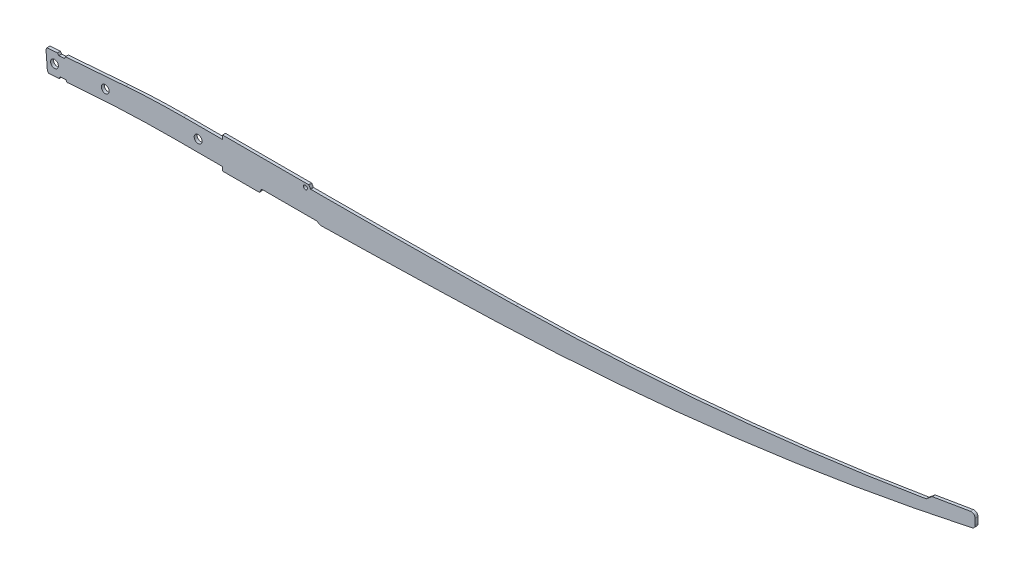
SolidWorks part; units mm, degrees
ref_plane "前视基准面" through (0, 0, 0) normal (0, 0, 1) x (1, 0, 0)
ref_plane "上视基准面" through (0, 0, 0) normal (0, 1, 0) x (1, 0, 0)
ref_plane "右视基准面" through (0, 0, 0) normal (1, 0, 0) x (0, 0, -1)
sketch "草图1" plane through (0, 0, 0) normal (0, 0, 1) x (1, 0, 0)
  line L0 (0, 81.9069) -> (0, 12) construction
  line L1 (0, 16) -> (88.2679, 16)
  line L2 (88.2679, 16) -> (90, 13)
  line L3 (0, -16) -> (37.6906, -16)
  line L4 (37.6906, -16) -> (40, -12)
  line L5 (40, -12) -> (96.5359, -12)
  line L6 (96.5359, -12) -> (100, -14)
  line L7 (0, 16) -> (0, 12)
  line L8 (-48.3677, 0) -> (26.6044, 0) construction
  line L9 (720, 53.5953) -> (726.0839, 58.6179)
  line L10 (726.0839, 58.6179) -> (770, 66)
  line L11 (770, 66) -> (770, 52)
  line L12 (90, 13) -> (0, 13) construction
  line L13 (720, 53.5953) -> (770, 62) construction
  line L14 (100, -14) -> (0, -14) construction
  line L15 (100, -14) -> (0, -15.7) construction
  line L16 (0, 12) -> (-40, 12)
  line L17 (0, -12) -> (-49.2119, -12)
  line L21 (0, -12) -> (0, -16)
  line L22 (0, 12) -> (0, 0) construction
  line L23 (0, -12) -> (0, -75.7106) construction
  line L24 (-99.0281, 9.7297) -> (-160.8449, 4.9675)
  line L27 (90, 13) -> (80.185, -4)
  line L28 (80.185, -4) -> (55.3812, -4)
  line L29 (55.3812, -4) -> (51.3397, 3)
  line L30 (51.3397, 3) -> (39.4226, 3)
  line L31 (39.4226, 3) -> (35.3812, -4)
  line L32 (35.3812, -4) -> (40, -12)
  line L33 (-140, -15.4919) -> (-159.1551, -16.9675)
  line L34 (-160.8449, 4.9675) -> (-160.6913, 2.9734) construction
  line L35 (0, 12) -> (0, -12)
  line L36 (4, 12) -> (4, -12)
  line L37 (4, -12) -> (35.3812, -12)
  line L38 (35.3812, -12) -> (30.7624, -4)
  line L39 (12, 12) -> (4, 12)
  line L41 (0, 8) -> (-36.5359, 8)
  line L42 (-40, 6) -> (-40, -6)
  line L43 (-36.5359, 8) -> (-40, 6)
  line L44 (16.6188, 12) -> (56.5359, 12)
  line L45 (16.6188, 12) -> (23.547, 0)
  line L46 (30.7624, -4) -> (21.2376, -4)
  line L47 (21.2376, -4) -> (12, 12)
  line L48 (23.547, 0) -> (33.0718, 0)
  line L49 (33.0718, 0) -> (37.1132, 7)
  line L50 (37.1132, 7) -> (53.6491, 7)
  line L51 (53.6491, 7) -> (56.5359, 12)
  line L52 (55.9585, 3) -> (57.6906, 0)
  line L53 (57.6906, 0) -> (77.8756, 0)
  line L54 (77.8756, 0) -> (82.4019, 7.8397)
  line L55 (80, 12) -> (61.1547, 12)
  line L56 (61.1547, 12) -> (55.9585, 3)
  line L57 (-160, -6) -> (-189.9114, -8.3043) construction
  line L58 (-160.8449, 4.9675) -> (-161.3826, 11.9468)
  line L59 (-189.9114, -8.3043) -> (-187.6898, 14.935)
  line L60 (-187.6898, 14.935) -> (-161.3826, 11.9468)
  line L61 (-184.1566, -30.9291) -> (-158.6174, -23.9468)
  line L62 (-189.9114, -8.3043) -> (-184.1566, -30.9291)
  line L63 (-159.1551, -16.9675) -> (-158.6174, -23.9468)
  line L64 (-161.8426, 2.8847) -> (-167.5164, 2.4476)
  line L65 (-168.8213, 4.353) -> (-167.5164, 2.4476)
  line L66 (-168.8213, 4.353) -> (-179.6345, 3.52)
  line L67 (-180.6322, 1.4372) -> (-179.2496, -16.5096)
  line L68 (-160.46, -15.0621) -> (-166.1338, -15.4992)
  line L69 (-167.1315, -17.582) -> (-166.1338, -15.4992)
  line L70 (-167.1315, -17.582) -> (-177.9447, -18.415)
  line L71 (-36.5359, -8) -> (-40, -6)
  line L72 (0, -8) -> (-36.5359, -8)
  line L73 (-160.4622, 0) -> (-160, -6) construction
  line L74 (-159.3087, -14.9734) -> (-159.1551, -16.9675) construction
  line L75 (-160.6913, 2.9734) -> (-160.4622, 0) construction
  line L76 (-160, -6) -> (-159.3087, -14.9734) construction
  line L77 (-160.8449, 4.9675) -> (-161.8426, 2.8847)
  line L78 (-160.6913, 2.9734) -> (-161.8426, 2.8847) construction
  line L79 (-159.1551, -16.9675) -> (-160.46, -15.0621)
  line L80 (-159.3087, -14.9734) -> (-160.46, -15.0621) construction
  line L81 (-180.6322, 1.4372) -> (-179.6345, 3.52)
  line L82 (-179.2496, -16.5096) -> (-177.9447, -18.415)
  line L83 (30.7624, -4) -> (35.3812, -4)
  line L84 (80, 12) -> (82.4019, 7.8397)
  line L85 (-187.6898, 14.935) -> (-184.1566, -30.9291) construction
  arc A0 (90, 13) -> (300, 14.8376) centre (90, 12013) ccw
  arc A1 (100, -14) -> (280, -9.3187) centre (-69.9754, 9984.5553) ccw
  arc A2 (300, 14.8376) -> (720, 53.5953) centre (250.428, 2847.0891) ccw
  arc A3 (280, -9.3187) -> (770, 52) centre (183.3078, 2751.817) ccw
  arc A4 (-4, 0) -> (-160, -6) centre (-4, -2031) ccw construction
  circle A8 centre (-25, -0.1086) radius 4.01
  circle A9 centre (-120, -3.3154) radius 4.01
  arc A11 (-40, 12) -> (-99.0281, 9.7297) centre (-40, -756.5) ccw
  arc A13 (-49.2119, -12) -> (-140, -15.4919) centre (-49.2119, -1193.9919) ccw
  circle A14 centre (-171.9645, -6.9217) radius 4.01
  circle A15 centre (84.8, 12) radius 2.01
  point P85 (-179.9409, -7.5362)
  point P97 (0, 0)
  point P98 (0, 0)
  dimension "D1" = 770
  dimension "D3" = 300
  dimension "D16" = 52
  dimension "D17" = 50
  dimension "D19" = 12000
  dimension "D20" = 10000
  dimension "D22" = 4
  dimension "D24" = 160
  dimension "D29" = 40
  dimension "D30" = 8.02
  dimension "D32" = 8.02
  dimension "D23" = 11
  dimension "D33" = 20
  dimension "D27" = 8.02
  dimension "D69" = 4.02
  dimension "D2" = 32
  dimension "D4" = 490
  dimension "D5" = 60
  dimension "D6" = 60
  dimension "D7" = 30
  dimension "D8" = 30
  dimension "D9" = 14
  dimension "D10" = 100
  dimension "D11" = 90
  dimension "D12" = 3
  dimension "D13" = 4
  dimension "D14" = 2
  dimension "D15" = 40
  dimension "D18" = 10
  dimension "D21" = 1.7
  dimension "D25" = 6
  dimension "D26" = 30
  dimension "D28" = 24
  dimension "D31" = 40
  dimension "D34" = 25
  dimension "D35" = 46
  dimension "D36" = 60
  dimension "D37" = 20
  dimension "D38" = 12
  dimension "D39" = 13
  dimension "D40" = 20
  dimension "D41" = 4
  dimension "D42" = 4
  dimension "D43" = 4
  dimension "D44" = 60
  dimension "D45" = 4
  dimension "D46" = 40
  dimension "D47" = 30
  dimension "D48" = 12
  dimension "D49" = 4
  dimension "D50" = 4
  dimension "D51" = 4
  dimension "D52" = 4
  dimension "D53" = 4
  dimension "D54" = 4
  dimension "D55" = 4
  dimension "D56" = 4
  dimension "D57" = 8
  dimension "D58" = 16
  dimension "D59" = 20
  dimension "D60" = 18
  dimension "D61" = 36
  dimension "D62" = 8
  dimension "D63" = 60
  dimension "D64" = 60
  dimension "D65" = 12
  dimension "D66" = 4
  dimension "D67" = 60
  dimension "D68" = 10
  dimension "D70" = 5.2
extrude "凸台-拉伸1" add sketch "草图1" along normal mid plane 3 contours L16 L17 L7 | A1 A3 L11 L10 L9 A2 A0 L2 L1 L7 L3 L4 L5 L6 | L7 L35 L21 L3 L4 L32 L31 L30 L29 L28 L27 L2 L1 | L42 L17 L35 L16 A8 | L72 L35 L41 L43 L42 L71 A8 | L46 L47 L39 L36 L37 L38 | L52 L53 L54 L84 L55 L56 | L44 L51 L50 L49 L48 L45 region at (39.09, 3.2882, 0) region at (-98.5983, -2.356, 0) region at (372.235, 12.2984, 0) region at (-19.3423, 0.0094, 0)
fillet "圆角1" radius 4 2 edges at (770, 66, 0) (770, 52, 0)
fillet "圆角2" radius 0.5 8 edges at (720, 53.5953, 0) (726.0839, 58.6179, 0) (40, -12, 0) (96.5359, -12, 0) (100, -14, 0) (90, 13, 0) (88.2679, 16, 0) (37.6906, -16, 0)
